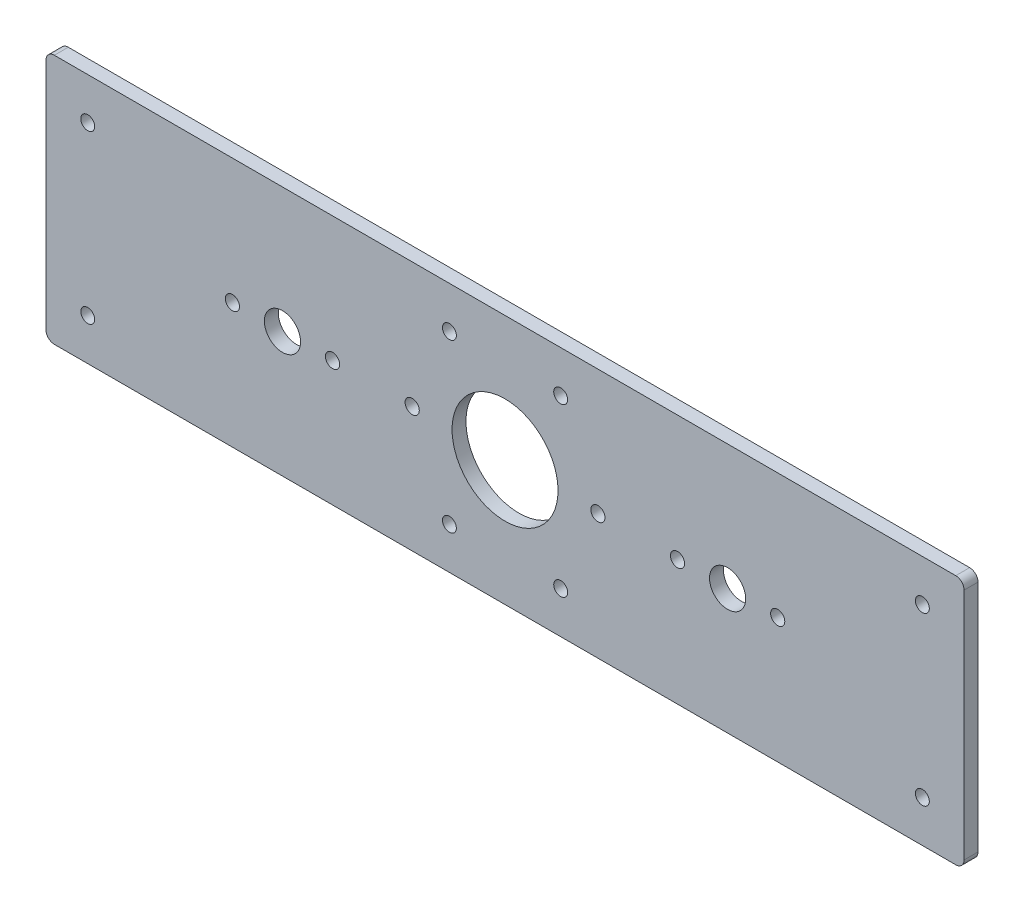
SolidWorks part; units mm, degrees
ref_plane "Front Plane" through (0, 0, 0) normal (0, 0, 1) x (1, 0, 0)
ref_plane "Top Plane" through (0, 0, 0) normal (0, 1, 0) x (1, 0, 0)
ref_plane "Right Plane" through (0, 0, 0) normal (1, 0, 0) x (0, 0, -1)
sketch "Sketch1" plane through (0, 0, 0) normal (0, 0, 1) x (1, 0, 0)
  line L0 (-165, 0) -> (165, 0) construction
  line L1 (165, -45) -> (-165, -45)
  line L2 (165, -45) -> (165, 45)
  line L3 (165, 45) -> (-165, 45)
  line L4 (-165, -45) -> (-165, 45)
  line L5 (165, -45) -> (-165, 45) construction
  line L6 (165, 45) -> (-165, -45) construction
  line L8 (0, -33.3754) -> (33.3754, 0) construction
  line L9 (0, -33.3754) -> (-33.3754, 0) construction
  line L10 (-33.3754, 0) -> (0, 33.3754) construction
  line L11 (33.3754, 0) -> (0, 33.3754) construction
  line L12 (0, -33.3754) -> (0, 33.3754) construction
  line L13 (-33.3754, 0) -> (33.3754, 0) construction
  circle A0 centre (0, 0) radius 19.05
  circle A1 centre (-33.3754, 0) radius 2.55
  circle A2 centre (33.3754, 0) radius 2.55
  point P0 (0, 0)
  dimension "D3" = 38.1
  dimension "D4" = 47.2
  dimension "D5" = 47.2
  dimension "D8" = 5.1
  dimension "D9" = 5.1
  dimension "D1" = 90
  dimension "D2" = 330
  dimension "D6" = 90
  dimension "D7" = 90
extrude "Boss-Extrude1" add sketch "Sketch1" along normal mid plane 5
sketch "Sketch2" plane through (0, 0, 2.5) normal (0, 0, 1) x (1, 0, 0)
  line L2 (-150, 45) -> (-150, -45)
  line L3 (-150, 45) -> (-150, -45) construction
  line L5 (150, -45) -> (150, 45)
  line L6 (150, -45) -> (150, 45) construction
  line L23 (165, 30) -> (-165, 30)
  line L24 (165, 30) -> (-165, 30) construction
  line L25 (0, 45) -> (0, -45) construction
  line L26 (-165, -30) -> (165, -30)
  line L27 (-165, -30) -> (165, -30) construction
  line L28 (165, 45) -> (-165, 45) construction
  line L29 (-165, -45) -> (165, -45) construction
  line L30 (-20, 45) -> (-20, -45) construction
  line L31 (20, 45) -> (20, -45) construction
  circle A0 centre (-150, 30) radius 2.5
  circle A1 centre (-150, -30) radius 2.5
  circle A2 centre (-20, 30) radius 2.5
  circle A3 centre (-20, -30) radius 2.5
  circle A4 centre (20, -30) radius 2.5
  circle A5 centre (20, 30) radius 2.5
  circle A6 centre (150, 30) radius 2.5
  circle A7 centre (150, -30) radius 2.5
  dimension "D7" = 5
  dimension "D8" = 5
  dimension "D9" = 5
  dimension "D10" = 5
  dimension "D11" = 5
  dimension "D12" = 5
  dimension "D13" = 5
  dimension "D14" = 5
  dimension "D1" = 15
  dimension "D2" = 15
  dimension "D3" = 15
  dimension "D4" = 15
  dimension "D5" = 20
  dimension "D6" = 20
extrude "Cut-Extrude1" cut sketch "Sketch2" against normal through all
sketch "Sketch3" plane through (0, 0, 2.5) normal (0, 0, 1) x (1, 0, 0)
  line L0 (0, 0) -> (-49.4534, 0) construction
  circle A0 centre (-62, 0) radius 2.55
  circle A1 centre (-98, 0) radius 2.55
  circle A2 centre (-80, 0) radius 6.5
  dimension "D1" = 5.1
  dimension "D2" = 5.1
  dimension "D3" = 13
  dimension "D4" = 80
  dimension "D5" = 18
  dimension "D6" = 18
extrude "Cut-Extrude2" cut sketch "Sketch3" against normal through all
mirror "Mirror1" about plane through (0, 0, 0) normal (1, 0, 0) of "Cut-Extrude2"
fillet "Fillet1" radius 3 4 edges at (-165, -45, 0) (165, -45, 0) (165, 45, 0) (-165, 45, 0)
equation "\"D4@Sketch3\"=160/2"
